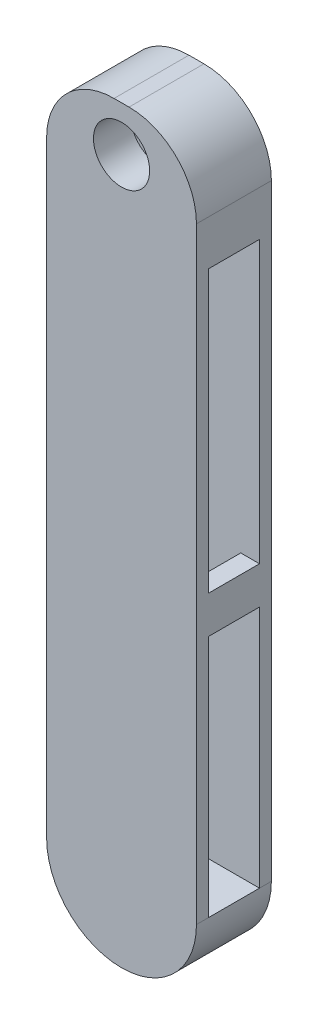
SolidWorks part; units mm, degrees
material "Acrylic (Medium-high impact)"
ref_plane "Front" through (0, 0, 0) normal (0, 0, 1) x (1, 0, 0)
ref_plane "Top" through (0, 0, 0) normal (0, 1, 0) x (1, 0, 0)
ref_plane "Right" through (0, 0, 0) normal (1, 0, 0) x (0, 0, -1)
sketch "Sketch2" plane through (0, 0, 0) normal (0, 0, 1) x (1, 0, 0)
  line L1 (-20, -100) -> (20, -100)
  line L2 (-20, -100) -> (-20, 100)
  line L3 (-20, 100) -> (20, 100)
  line L4 (20, -100) -> (20, 100)
  line L5 (-20, -100) -> (20, 100) construction
  line L6 (-20, 100) -> (20, -100) construction
  point P1 (0, 0)
  dimension "D1" = 200
  dimension "D2" = 40
extrude "Boss-Extrude1" add sketch "Sketch2" along normal blind 20
sketch "Sketch3" plane through (0, 0, 0) normal (0, 0, -1) x (-1, 0, 0)
  line L0 (20, -100) -> (-20, -100) construction
  circle A0 centre (0, -90) radius 2
  dimension "D1" = 4
  dimension "D2" = 10
extrude "Cut-Extrude1" cut sketch "Sketch3" against normal blind 10
fillet "Fillet1" radius 20 2 edges at (20, -100, 10) (-20, -100, 10)
sketch "Sketch5" plane through (0, 0, 20) normal (0, 0, 1) x (1, 0, 0)
  line L0 (20, -80) -> (20, 100) construction
  line L1 (20, 100) -> (-20, 100) construction
  circle A0 centre (0, 88) radius 7.5
  dimension "D1" = 15
  dimension "D2" = 20
  dimension "D3" = 12
extrude "Cut-Extrude3" cut sketch "Sketch5" against normal blind 10
fillet "Fillet2" radius 18 2 edges at (20, 100, 10) (-20, 100, 10)
sketch "Sketch6" plane through (-20, 0, 0) normal (-1, 0, 0) x (0, 0, 1)
  line L0 (0, -80) -> (20, -80) construction
  line L1 (3.175, -80) -> (16.825, -80)
  line L2 (3.175, -80) -> (3.175, 70)
  line L3 (3.175, 70) -> (16.825, 70)
  line L4 (16.825, -80) -> (16.825, 70)
  line L5 (0, 82) -> (0, -80) construction
  line L6 (16.825, 70) -> (23.175, 70) construction
  line L7 (3.175, 70) -> (-3.175, 70) construction
  line L9 (20, 82) -> (20, -80) construction
  dimension "D1" = 3.175
  dimension "D2" = 150
  dimension "D3" = 3.175
extrude "Cut-Extrude4" cut sketch "Sketch6" against normal through all
sketch "Sketch7" plane through (0, 0, 16.825) normal (0, 0, -1) x (-1, 0, 0)
  line L0 (20, -80) -> (20, 70) construction
  line L2 (20, -5) -> (15, -5)
  line L3 (20, -5) -> (20, -15)
  line L4 (20, -15) -> (15, -15)
  line L5 (15, -5) -> (15, -15)
  dimension "D1" = 5
  dimension "D2" = 10
extrude "Boss-Extrude2" add sketch "Sketch7" along normal blind 15
mirror "Mirror1" about plane through (0, 0, 0) normal (1, 0, 0) of "Boss-Extrude2"
